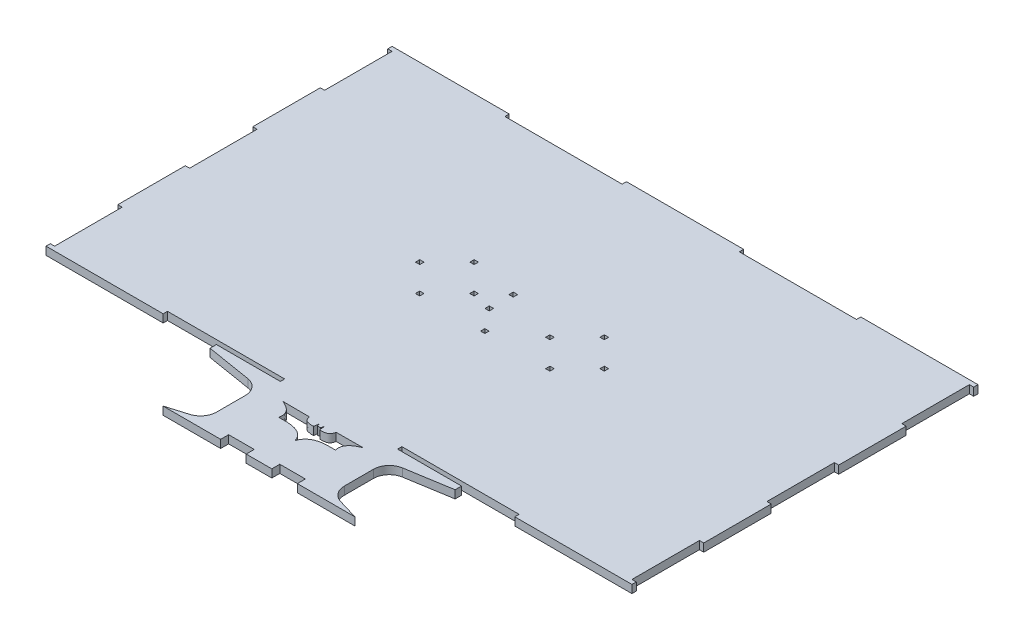
SolidWorks part; units mm, degrees
ref_plane "Front Plane" through (0, 0, 0) normal (0, 0, 1) x (1, 0, 0)
ref_plane "Top Plane" through (0, 0, 0) normal (0, 1, 0) x (1, 0, 0)
ref_plane "Right Plane" through (0, 0, 0) normal (1, 0, 0) x (0, 0, -1)
sketch "Sketch1" plane through (0, 0, 0) normal (0, 1, 0) x (1, 0, 0)
  line L0 (-183.2, 108.2) -> (-109.92, 108.2)
  line L1 (-109.92, 105.5) -> (-36.64, 105.5)
  line L4 (180.5, 105.5) -> (180.5, 63.3)
  line L5 (183.2, 108.2) -> (183.2, 105.5)
  line L8 (183.2, 63.3) -> (183.2, 21.1)
  line L9 (183.2, 108.2) -> (183.2, -108.2) construction
  line L10 (180.5, -105.5) -> (183.2, -105.5)
  line L11 (180.5, 105.5) -> (183.2, 105.5)
  line L13 (180.5, 105.5) -> (180.5, -105.5) construction
  line L14 (180.5, 21.1) -> (180.5, -21.1)
  line L16 (180.5, -63.3) -> (180.5, -105.5)
  line L18 (-180.5, 105.5) -> (-180.5, -105.5) construction
  line L23 (-183.2, 108.2) -> (183.2, 108.2) construction
  line L24 (-36.64, 108.2) -> (36.64, 108.2)
  line L26 (109.92, 108.2) -> (183.2, 108.2)
  line L27 (-109.92, 108.2) -> (-109.92, 105.5)
  line L28 (-36.64, 108.2) -> (-36.64, 105.5)
  line L29 (36.64, 108.2) -> (36.64, 105.5)
  line L30 (109.92, 108.2) -> (109.92, 105.5)
  line L31 (-180.5, 105.5) -> (180.5, 105.5) construction
  line L32 (36.64, 105.5) -> (109.92, 105.5)
  line L33 (-183.2, -108.2) -> (183.2, -108.2) construction
  line L34 (-180.5, -105.5) -> (180.5, -105.5) construction
  line L35 (180.5, -21.1) -> (183.2, -21.1)
  line L36 (109.92, -108.2) -> (183.2, -108.2)
  line L37 (109.92, -108.2) -> (109.92, -105.5)
  line L38 (36.64, -105.5) -> (109.92, -105.5)
  line L39 (36.64, -108.2) -> (36.64, -105.5)
  line L41 (-36.64, -108.2) -> (-36.64, -105.5)
  line L42 (-109.92, -105.5) -> (-36.64, -105.5)
  line L43 (-109.92, -108.2) -> (-109.92, -105.5)
  line L44 (-183.2, -108.2) -> (-109.92, -108.2)
  line L45 (180.5, -63.3) -> (183.2, -63.3)
  line L46 (180.5, 21.1) -> (183.2, 21.1)
  line L47 (180.5, 63.3) -> (183.2, 63.3)
  line L48 (183.2, -21.1) -> (183.2, -63.3)
  line L49 (-183.2, 108.2) -> (-183.2, -108.2) construction
  line L50 (183.2, -105.5) -> (183.2, -108.2)
  line L51 (-40, -126.6956) -> (-40, -144.7597)
  line L52 (-183.2, -105.5) -> (-183.2, -108.2)
  line L53 (-180.5, -105.5) -> (-183.2, -105.5)
  line L54 (-180.5, -63.3) -> (-180.5, -105.5)
  line L55 (-180.5, -63.3) -> (-183.2, -63.3)
  line L56 (-183.2, -21.1) -> (-183.2, -63.3)
  line L57 (-180.5, -21.1) -> (-183.2, -21.1)
  line L58 (-180.5, 21.1) -> (-180.5, -21.1)
  line L59 (-180.5, 21.1) -> (-183.2, 21.1)
  line L60 (-183.2, 63.3) -> (-183.2, 21.1)
  line L61 (-180.5, 63.3) -> (-183.2, 63.3)
  line L62 (-180.5, 105.5) -> (-180.5, 63.3)
  line L63 (-183.2, 108.2) -> (-183.2, 105.5)
  line L64 (-180.5, 105.5) -> (-183.2, 105.5)
  line L67 (40, -126.6956) -> (40, -144.7597)
  line L70 (-40, -158.2) -> (-24, -158.2)
  line L71 (24, -153.2) -> (8, -153.2)
  line L75 (-8, -158.2) -> (8, -158.2)
  line L77 (24, -158.2) -> (40, -158.2)
  line L78 (-24, -158.2) -> (-24, -153.2)
  line L79 (-8, -158.2) -> (-8, -153.2)
  line L80 (8, -158.2) -> (8, -153.2)
  line L81 (24, -158.2) -> (24, -153.2)
  line L82 (-8, -153.2) -> (-24, -153.2)
  line L83 (-36.64, -108.2) -> (-76.64, -108.2)
  line L84 (36.64, -108.2) -> (76.64, -108.2)
  line L85 (-76.64, -108.2) -> (-76.64, -112.2)
  line L86 (-76.64, -112.2) -> (-48.384, -116.8271)
  line L87 (76.64, -108.2) -> (76.64, -112.2)
  line L88 (76.64, -112.2) -> (48.384, -116.8271)
  line L89 (-40, -158.2) -> (-60, -158.2)
  line L90 (40, -158.2) -> (60, -158.2)
  line L92 (-47.1265, -154.338) -> (-60, -158.2)
  line L94 (47.1265, -154.338) -> (60, -158.2)
  line L95 (0.9301, -120.7166) -> (0, -120.6808)
  line L196 (1.4468, -118.9339) -> (0.9301, -120.7166)
  line L197 (25.0098, -118.2105) -> (8.3452, -118.288)
  line L198 (1.5053, -118.7321) -> (1.5244, -118.908)
  line L199 (1.5053, -118.7321) -> (1.4468, -118.9339)
  line L200 (-1.5053, -118.7321) -> (-1.4468, -118.9339)
  line L201 (-1.5053, -118.7321) -> (-1.5244, -118.908)
  line L202 (-25.0098, -118.2105) -> (-8.3452, -118.288)
  line L203 (-1.4468, -118.9339) -> (-0.9301, -120.7166)
  line L204 (-0.9301, -120.7166) -> (0, -120.6808)
  line L205 (56.3537, 1.35) -> (56.3537, -1.35)
  line L206 (56.3537, -1.35) -> (59.0537, -1.35)
  line L207 (59.0537, -1.35) -> (59.0537, 1.35)
  line L208 (59.0537, 1.35) -> (56.3537, 1.35)
  line L209 (39.3537, 18.35) -> (39.3537, 15.65)
  line L210 (39.3537, 15.65) -> (42.0537, 15.65)
  line L211 (42.0537, 15.65) -> (42.0537, 18.35)
  line L212 (42.0537, 18.35) -> (39.3537, 18.35)
  line L213 (39.3537, -15.65) -> (39.3537, -18.35)
  line L214 (39.3537, -18.35) -> (42.0537, -18.35)
  line L215 (42.0537, -18.35) -> (42.0537, -15.65)
  line L216 (42.0537, -15.65) -> (39.3537, -15.65)
  line L217 (22.3537, 1.35) -> (22.3537, -1.35)
  line L218 (22.3537, -1.35) -> (25.0537, -1.35)
  line L219 (25.0537, -1.35) -> (25.0537, 1.35)
  line L220 (25.0537, 1.35) -> (22.3537, 1.35)
  line L221 (-25.0537, 1.35) -> (-22.3537, 1.35)
  line L223 (-25.0537, -1.35) -> (-25.0537, 1.35)
  line L224 (-22.3537, -1.35) -> (-25.0537, -1.35)
  line L225 (-22.3537, 1.35) -> (-22.3537, -1.35)
  line L226 (-42.0537, -15.65) -> (-39.3537, -15.65)
  line L227 (-42.0537, -18.35) -> (-42.0537, -15.65)
  line L228 (-39.3537, -18.35) -> (-42.0537, -18.35)
  line L229 (-39.3537, -15.65) -> (-39.3537, -18.35)
  line L230 (-42.0537, 18.35) -> (-39.3537, 18.35)
  line L231 (-42.0537, 15.65) -> (-42.0537, 18.35)
  line L232 (-39.3537, 15.65) -> (-42.0537, 15.65)
  line L233 (-39.3537, 18.35) -> (-39.3537, 15.65)
  line L234 (-59.0537, 1.35) -> (-56.3537, 1.35)
  line L235 (-59.0537, -1.35) -> (-59.0537, 1.35)
  line L236 (-56.3537, -1.35) -> (-59.0537, -1.35)
  line L237 (-56.3537, 1.35) -> (-56.3537, -1.35)
  line L250 (1.3481, -18.3469) -> (1.3481, -15.6469)
  line L263 (-1.3519, -18.3469) -> (1.3481, -18.3469)
  line L264 (-1.3519, -15.6469) -> (-1.3519, -18.3469)
  line L265 (1.3481, -15.6469) -> (-1.3519, -15.6469)
  line L266 (-9.5244, 10.3029) -> (-9.5244, 13.0029)
  line L267 (-12.2244, 10.3029) -> (-9.5244, 10.3029)
  line L268 (-12.2244, 13.0029) -> (-12.2244, 10.3029)
  line L269 (-9.5244, 13.0029) -> (-12.2244, 13.0029)
  line L270 (-9.5244, -4.6971) -> (-9.5244, -1.9971)
  line L271 (-12.2244, -4.6971) -> (-9.5244, -4.6971)
  line L272 (-12.2244, -1.9971) -> (-12.2244, -4.6971)
  line L273 (-9.5244, -1.9971) -> (-12.2244, -1.9971)
  arc A0 (-48.384, -116.8271) -> (-40, -126.6956) centre (-50, -126.6956) cw
  arc A1 (40, -126.6956) -> (48.384, -116.8271) centre (50, -126.6956) cw
  arc A2 (-47.1265, -154.338) -> (-40, -144.7597) centre (-50, -144.7597) ccw
  arc A3 (40, -144.7597) -> (47.1265, -154.338) centre (50, -144.7597) ccw
  spline S0 degree 3 poles (0, -135.7277) (-0.2584, -135.0818) (-0.4466, -134.4031) (-0.7751, -133.7899) (-1.0966, -133.1898) (-1.4897, -132.6232) (-1.9377, -132.1105) (-2.391, -131.5919) (-2.9056, -131.1213) (-3.4621, -130.7154) (-4.0576, -130.281) (-4.6993, -129.9012) (-5.374, -129.6044) (-6.2141, -129.2348) (-7.0911, -128.9401) (-7.9835, -128.7259) (-9.0354, -128.4735) (-10.1097, -128.3041) (-11.1872, -128.2092) (-12.586, -128.0861) (-13.9951, -128.0606) (-15.3986, -128.1059) (-16.1735, -128.1309) (-16.9488, -128.1403) (-17.7239, -128.1575) knots 0 0 0 0 1 1 1 2 2 2 3 3 3 4 4 4 5 5 5 6 6 6 7 7 7 8 8 8 8
  spline S1 degree 3 poles (-17.7239, -128.1575) (-17.6464, -127.503) (-17.4868, -126.853) (-17.4914, -126.194) (-17.4955, -125.602) (-17.5727, -125.0019) (-17.7497, -124.4371) (-17.9387, -123.8343) (-18.2232, -123.2555) (-18.5765, -122.7319) (-18.9621, -122.1603) (-19.4328, -121.6422) (-19.9459, -121.1817) (-20.533, -120.6546) (-21.1783, -120.1875) (-21.8578, -119.7865) (-22.8694, -119.1894) (-23.9755, -118.7674) (-25.0098, -118.2105) knots 0 0 0 0 1 1 1 2 2 2 3 3 3 4 4 4 5 5 5 6 6 6 6
  spline S2 degree 3 poles (2.0928, -122.1118) (2.0066, -121.9998) (1.8591, -121.915) (1.8344, -121.7759) (1.6664, -120.8292) (1.6277, -119.864) (1.5244, -118.908) knots 0 0 0 0 1 1 1 2 2 2 2
  spline S3 degree 3 poles (8.3452, -118.288) (8.173, -118.8564) (8.0758, -119.4532) (7.8285, -119.9932) (7.6484, -120.3864) (7.396, -120.758) (7.0792, -121.0525) (6.7709, -121.3391) (6.397, -121.5764) (5.9941, -121.6984) (5.1566, -121.952) (4.2806, -122.0712) (3.4104, -122.1635) (2.9733, -122.2098) (2.532, -122.129) (2.0928, -122.1118) knots 0 0 0 0 1 1 1 2 2 2 3 3 3 4 4 4 5 5 5 5
  spline S4 degree 3 poles (17.7239, -128.1575) (17.6464, -127.503) (17.4868, -126.853) (17.4914, -126.194) (17.4955, -125.602) (17.5727, -125.0019) (17.7497, -124.4371) (17.9387, -123.8343) (18.2232, -123.2555) (18.5765, -122.7319) (18.9621, -122.1603) (19.4328, -121.6422) (19.9459, -121.1817) (20.533, -120.6546) (21.1783, -120.1875) (21.8578, -119.7865) (22.8694, -119.1894) (23.9755, -118.7674) (25.0098, -118.2105) knots 0 0 0 0 1 1 1 2 2 2 3 3 3 4 4 4 5 5 5 6 6 6 6
  spline S5 degree 3 poles (-8.3452, -118.288) (-8.173, -118.8564) (-8.0758, -119.4532) (-7.8285, -119.9932) (-7.6484, -120.3864) (-7.396, -120.758) (-7.0792, -121.0525) (-6.7709, -121.3391) (-6.397, -121.5764) (-5.9941, -121.6984) (-5.1566, -121.952) (-4.2806, -122.0712) (-3.4104, -122.1635) (-2.9733, -122.2098) (-2.532, -122.129) (-2.0928, -122.1118) knots 0 0 0 0 1 1 1 2 2 2 3 3 3 4 4 4 5 5 5 5
  spline S6 degree 3 poles (-2.0928, -122.1118) (-2.0066, -121.9998) (-1.8591, -121.915) (-1.8344, -121.7759) (-1.6664, -120.8292) (-1.6277, -119.864) (-1.5244, -118.908) knots 0 0 0 0 1 1 1 2 2 2 2
  spline S7 degree 3 poles (0, -135.7277) (0.2584, -135.0818) (0.4466, -134.4031) (0.7751, -133.7899) (1.0966, -133.1898) (1.4897, -132.6232) (1.9377, -132.1105) (2.391, -131.5919) (2.9056, -131.1213) (3.4621, -130.7154) (4.0576, -130.281) (4.6993, -129.9012) (5.374, -129.6044) (6.2141, -129.2348) (7.0911, -128.9401) (7.9835, -128.7259) (9.0354, -128.4735) (10.1097, -128.3041) (11.1872, -128.2092) (12.586, -128.0861) (13.9951, -128.0606) (15.3986, -128.1059) (16.1735, -128.1309) (16.9488, -128.1403) (17.7239, -128.1575) knots 0 0 0 0 1 1 1 2 2 2 3 3 3 4 4 4 5 5 5 6 6 6 7 7 7 8 8 8 8
  point P0 (0, 0)
  point P58 (-40, -118.2)
  point P68 (40, -118.2)
  point P78 (0, 0)
  dimension "D2" = 10
  dimension "D3" = 10
  dimension "D6" = 10
  dimension "D7" = 10
  dimension "D1" = 2.7
  dimension "D4" = 40
  dimension "D5" = 40
extrude "Boss-Extrude1" add sketch "Sketch1" along normal blind 5
